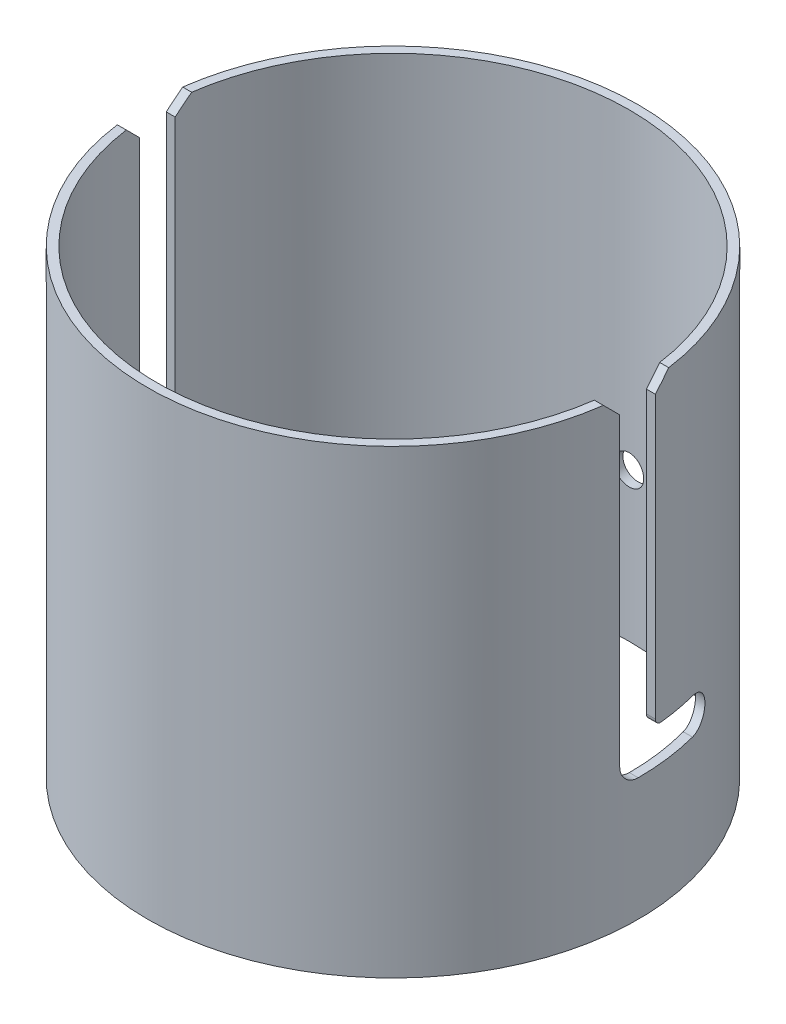
SolidWorks part; units mm, degrees
material "6061-T6 (SS)"
ref_plane "Front Plane" through (0, 0, 0) normal (0, 0, 1) x (1, 0, 0)
ref_plane "Top Plane" through (0, 0, 0) normal (0, 1, 0) x (1, 0, 0)
ref_plane "Right Plane" through (0, 0, 0) normal (1, 0, 0) x (0, 0, -1)
sketch "Sketch2" plane through (0, 0, 0) normal (1, 0, 0) x (0, 0, -1)
  line L0 (-79.55, 0) -> (-82.55, 0)
  line L1 (-82.55, 0) -> (-82.55, 155)
  line L2 (-82.55, 155) -> (-79.55, 155)
  line L5 (-79.55, 155) -> (-79.55, 0)
  dimension "D1" = 82.55
  dimension "D2" = 155
  dimension "D3" = 3
ref_axis "Axis1" through (0, -7.75, 0) along (0, 1, 0)
revolve "Revolve1" add sketch "Sketch2" angle 360 about axis through (0, -7.75, 0) along (0, 1, 0)
sketch "Sketch3" plane through (0, 0, 0) normal (1, 0, 0) x (0, 0, -1)
  line L0 (-6, 155) -> (6, 155)
  line L1 (82.55, 155) -> (-82.55, 155) construction
  line L2 (6, 155) -> (6, 41.3)
  line L3 (6, 41.3) -> (-21, 41.3)
  line L4 (-21, 41.3) -> (-21, 53.3) construction
  line L5 (-21, 53.3) -> (-6, 53.3)
  line L6 (-6, 53.3) -> (-6, 155)
  line L7 (0, -7.75) -> (0, 162.75) construction
  line L8 (0, 0) -> (0, 47.5309) construction
  arc A0 (-21, 53.3) -> (-21, 41.3) centre (-21, 47.3) ccw
  dimension "D5" = 12
  dimension "D1" = 101.7
  dimension "D2" = 12
  dimension "D4" = 15
extrude "Cut-Extrude1" cut sketch "Sketch3" against normal through all
fillet "Fillet1" radius 6 1 edges at (-80.8275, 41.3, -6)
chamfer "Chamfer1" distance 5 angle 45 2 edges at (-80.8275, 155, 6) (-80.8275, 155, -6)
fillet "Fillet4" radius 2 1 edges at (-80.8275, 53.3, 6)
pattern_circular "CirPattern1" count 2 over 360 about axis through (0, -7.75, 0) along (0, 1, 0) of "Cut-Extrude1", "Fillet1", "Chamfer1", "Fillet4"
sketch "Sketch4" plane through (0, 0, 0) normal (0, 0, 1) x (1, 0, 0)
  line L0 (-79.55, 0) -> (79.55, 0) construction
  line L1 (-82.3317, 47.3) -> (-82.3317, 150) construction
  circle A0 centre (0, 50) radius 5
  dimension "D1" = 10
  dimension "D2" = 50
  dimension "D3" = 82.3317
extrude "Cut-Extrude2" cut sketch "Sketch4" against normal blind 100
equation "\"TubeDiameter\" = 6.500in"
equation "\"D1@Sketch2\"=\"TubeDiameter\"/2"
